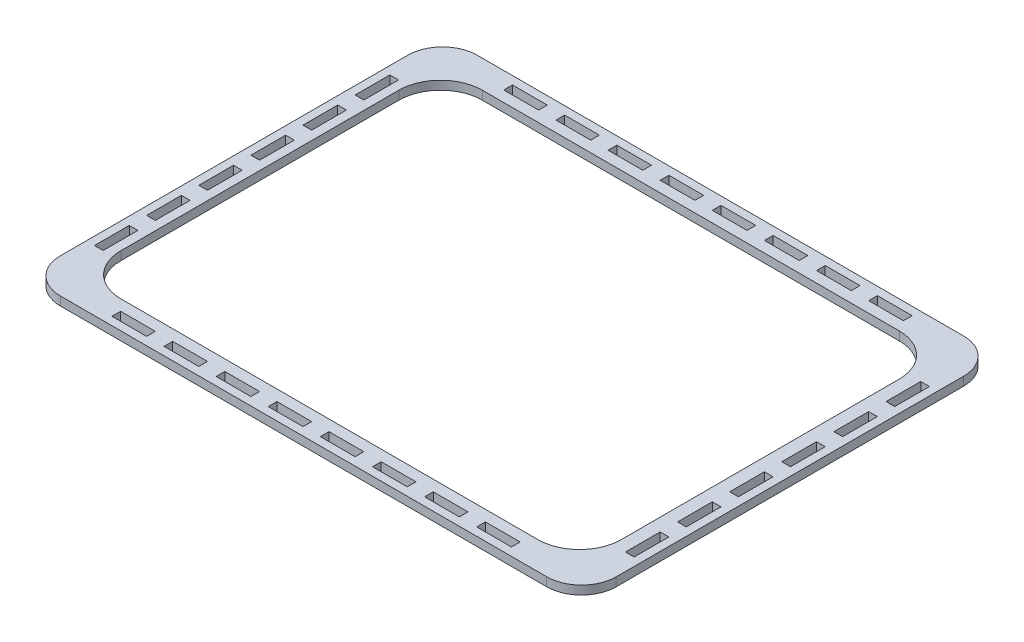
SolidWorks part; units mm, degrees
ref_plane "Front Plane" through (0, 0, 0) normal (0, 0, 1) x (1, 0, 0)
ref_plane "Top Plane" through (0, 0, 0) normal (0, 1, 0) x (1, 0, 0)
ref_plane "Right Plane" through (0, 0, 0) normal (1, 0, 0) x (0, 0, -1)
ref_plane "MaskPlane" through (0, 7.1437, 0) normal (0, 1, 0) x (1, 0, 0)
sketch "Sketch1" plane through (0, 7.1437, 0) normal (0, 1, 0) x (-1, 0, 0)
  line L19 (-90.75, 50.8) -> (-90.75, 0)
  line L25 (-90.75, 50.8) -> (-90.75, 0)
  line L27 (-90.75, 0) -> (-90.75, -50.8)
  line L44 (-101.6, 63.5) -> (-101.6, -63.5) construction
  line L45 (-88.9, -76.2) -> (88.9, -76.2) construction
  line L46 (101.6, -63.5) -> (101.6, 63.5) construction
  line L47 (88.9, 76.2) -> (-88.9, 76.2) construction
  line L52 (-101.6, 63.5) -> (-101.6, -63.5)
  line L53 (-88.9, -76.2) -> (88.9, -76.2)
  line L54 (101.6, -63.5) -> (101.6, 63.5)
  line L55 (88.9, 76.2) -> (-88.9, 76.2)
  line L168 (-90.75, 0) -> (-90.75, -50.8)
  line L176 (-75.5, -66.05) -> (76.9, -66.05)
  line L177 (-75.5, -66.05) -> (76.9, -66.05)
  line L178 (92.15, -50.8) -> (92.15, 50.8)
  line L179 (92.15, -50.8) -> (92.15, 50.8)
  line L180 (76.9, 66.05) -> (-75.5, 66.05)
  line L181 (76.9, 66.05) -> (-75.5, 66.05)
  arc A4 (-88.9, 76.2) -> (-101.6, 63.5) centre (-88.9, 63.5) ccw construction
  arc A6 (-101.6, -63.5) -> (-88.9, -76.2) centre (-88.9, -63.5) ccw construction
  arc A8 (88.9, -76.2) -> (101.6, -63.5) centre (88.9, -63.5) ccw construction
  arc A10 (101.6, 63.5) -> (88.9, 76.2) centre (88.9, 63.5) ccw construction
  arc A16 (-88.9, 76.2) -> (-101.6, 63.5) centre (-88.9, 63.5) ccw
  arc A17 (-101.6, -63.5) -> (-88.9, -76.2) centre (-88.9, -63.5) ccw
  arc A18 (88.9, -76.2) -> (101.6, -63.5) centre (88.9, -63.5) ccw
  arc A19 (101.6, 63.5) -> (88.9, 76.2) centre (88.9, 63.5) ccw
  arc A24 (-90.75, -50.8) -> (-75.5, -66.05) centre (-75.5, -50.8) ccw
  arc A26 (-90.75, -50.8) -> (-75.5, -66.05) centre (-75.5, -50.8) ccw
  arc A132 (76.9, -66.05) -> (92.15, -50.8) centre (76.9, -50.8) ccw
  arc A134 (76.9, -66.05) -> (92.15, -50.8) centre (76.9, -50.8) ccw
  arc A140 (92.15, 50.8) -> (76.9, 66.05) centre (76.9, 50.8) ccw
  arc A141 (92.15, 50.8) -> (76.9, 66.05) centre (76.9, 50.8) ccw
  arc A142 (-75.5, 66.05) -> (-90.75, 50.8) centre (-75.5, 50.8) ccw
  arc A143 (-75.5, 66.05) -> (-90.75, 50.8) centre (-75.5, 50.8) ccw
  dimension "D1" = 3
extrude "FrontFace" add sketch "Sketch1" along normal blind 3.175
sketch "Sketch2" plane through (0, 10.3187, 0) normal (0, 1, 0) x (1, 0, 0)
  line L1 (-98.6155, 53.975) -> (-95.4405, 53.975)
  line L2 (-98.6155, 53.975) -> (-98.6155, -53.975)
  line L3 (-98.6155, -53.975) -> (-95.4405, -53.975)
  line L4 (-95.4405, 53.975) -> (-95.4405, -53.975)
  line L5 (-73.025, -70.0405) -> (73.025, -70.0405)
  line L6 (-73.025, -70.0405) -> (-73.025, -73.2155)
  line L7 (-73.025, -73.2155) -> (73.025, -73.2155)
  line L8 (73.025, -70.0405) -> (73.025, -73.2155)
  line L9 (95.4405, -53.975) -> (98.6155, -53.975)
  line L10 (95.4405, -53.975) -> (95.4405, 53.975)
  line L11 (95.4405, 53.975) -> (98.6155, 53.975)
  line L12 (98.6155, -53.975) -> (98.6155, 53.975)
  line L13 (73.025, 73.2155) -> (-73.025, 73.2155)
  line L14 (73.025, 73.2155) -> (73.025, 70.0405)
  line L15 (73.025, 70.0405) -> (-73.025, 70.0405)
  line L16 (-73.025, 73.2155) -> (-73.025, 70.0405)
  line L132 (95.25, -53.975) -> (101.6, -53.975)
  line L133 (95.25, -60.325) -> (95.25, -53.975)
  line L134 (101.6, -60.325) -> (95.25, -60.325)
  line L135 (101.6, -63.5) -> (101.6, -60.325)
  line L136 (79.375, -76.2) -> (88.9, -76.2)
  line L137 (79.375, -69.85) -> (79.375, -76.2)
  line L138 (73.025, -69.85) -> (79.375, -69.85)
  line L139 (73.025, -76.2) -> (73.025, -69.85)
  line L140 (60.325, -76.2) -> (73.025, -76.2)
  line L141 (60.325, -69.85) -> (60.325, -76.2)
  line L142 (53.975, -69.85) -> (60.325, -69.85)
  line L143 (53.975, -76.2) -> (53.975, -69.85)
  line L144 (41.275, -76.2) -> (53.975, -76.2)
  line L145 (41.275, -69.85) -> (41.275, -76.2)
  line L146 (34.925, -69.85) -> (41.275, -69.85)
  line L147 (34.925, -76.2) -> (34.925, -69.85)
  line L148 (22.225, -76.2) -> (34.925, -76.2)
  line L149 (22.225, -69.85) -> (22.225, -76.2)
  line L150 (15.875, -69.85) -> (22.225, -69.85)
  line L151 (15.875, -76.2) -> (15.875, -69.85)
  line L152 (3.175, -76.2) -> (15.875, -76.2)
  line L153 (3.175, -69.85) -> (3.175, -76.2)
  line L154 (-3.175, -69.85) -> (3.175, -69.85)
  line L155 (-3.175, -76.2) -> (-3.175, -69.85)
  line L156 (-15.875, -76.2) -> (-3.175, -76.2)
  line L157 (-15.875, -69.85) -> (-15.875, -76.2)
  line L158 (-22.225, -69.85) -> (-15.875, -69.85)
  line L159 (-22.225, -76.2) -> (-22.225, -69.85)
  line L160 (-34.925, -76.2) -> (-22.225, -76.2)
  line L161 (-34.925, -69.85) -> (-34.925, -76.2)
  line L162 (-41.275, -69.85) -> (-34.925, -69.85)
  line L163 (-41.275, -76.2) -> (-41.275, -69.85)
  line L164 (-53.975, -76.2) -> (-41.275, -76.2)
  line L165 (-53.975, -69.85) -> (-53.975, -76.2)
  line L166 (-60.325, -69.85) -> (-53.975, -69.85)
  line L167 (-60.325, -76.2) -> (-60.325, -69.85)
  line L168 (-73.025, -76.2) -> (-60.325, -76.2)
  line L169 (-73.025, -69.85) -> (-73.025, -76.2)
  line L170 (-79.375, -69.85) -> (-73.025, -69.85)
  line L171 (-79.375, -76.2) -> (-79.375, -69.85)
  line L172 (-88.9, -76.2) -> (-79.375, -76.2)
  line L173 (-101.6, -60.325) -> (-101.6, -63.5)
  line L174 (-95.25, -60.325) -> (-101.6, -60.325)
  line L175 (-95.25, -53.975) -> (-95.25, -60.325)
  line L176 (-101.6, -53.975) -> (-95.25, -53.975)
  line L177 (-101.6, -41.275) -> (-101.6, -53.975)
  line L178 (-95.25, -41.275) -> (-101.6, -41.275)
  line L179 (-95.25, -34.925) -> (-95.25, -41.275)
  line L180 (-101.6, -34.925) -> (-95.25, -34.925)
  line L181 (-101.6, -22.225) -> (-101.6, -34.925)
  line L182 (-95.25, -22.225) -> (-101.6, -22.225)
  line L183 (-95.25, -15.875) -> (-95.25, -22.225)
  line L184 (-101.6, -15.875) -> (-95.25, -15.875)
  line L185 (-101.6, -3.175) -> (-101.6, -15.875)
  line L186 (-95.25, -3.175) -> (-101.6, -3.175)
  line L187 (-95.25, 3.175) -> (-95.25, -3.175)
  line L188 (-101.6, 3.175) -> (-95.25, 3.175)
  line L189 (-101.6, 15.875) -> (-101.6, 3.175)
  line L190 (-95.25, 15.875) -> (-101.6, 15.875)
  line L191 (-95.25, 22.225) -> (-95.25, 15.875)
  line L192 (-101.6, 22.225) -> (-95.25, 22.225)
  line L193 (-101.6, 34.925) -> (-101.6, 22.225)
  line L194 (-95.25, 34.925) -> (-101.6, 34.925)
  line L195 (-95.25, 41.275) -> (-95.25, 34.925)
  line L196 (-101.6, 41.275) -> (-95.25, 41.275)
  line L197 (-101.6, 53.975) -> (-101.6, 41.275)
  line L198 (-95.25, 53.975) -> (-101.6, 53.975)
  line L199 (-95.25, 60.325) -> (-95.25, 53.975)
  line L200 (-101.6, 60.325) -> (-95.25, 60.325)
  line L201 (-101.6, 63.5) -> (-101.6, 60.325)
  line L202 (-79.375, 76.2) -> (-88.9, 76.2)
  line L203 (-79.375, 69.85) -> (-79.375, 76.2)
  line L204 (-73.025, 69.85) -> (-79.375, 69.85)
  line L205 (-73.025, 76.2) -> (-73.025, 69.85)
  line L206 (-60.325, 76.2) -> (-73.025, 76.2)
  line L207 (-60.325, 69.85) -> (-60.325, 76.2)
  line L208 (-53.975, 69.85) -> (-60.325, 69.85)
  line L209 (-53.975, 76.2) -> (-53.975, 69.85)
  line L210 (-41.275, 76.2) -> (-53.975, 76.2)
  line L211 (-41.275, 69.85) -> (-41.275, 76.2)
  line L212 (-34.925, 69.85) -> (-41.275, 69.85)
  line L213 (-34.925, 76.2) -> (-34.925, 69.85)
  line L214 (-22.225, 76.2) -> (-34.925, 76.2)
  line L215 (-22.225, 69.85) -> (-22.225, 76.2)
  line L216 (-15.875, 69.85) -> (-22.225, 69.85)
  line L217 (-15.875, 76.2) -> (-15.875, 69.85)
  line L218 (-3.175, 76.2) -> (-15.875, 76.2)
  line L219 (-3.175, 69.85) -> (-3.175, 76.2)
  line L220 (3.175, 69.85) -> (-3.175, 69.85)
  line L221 (3.175, 76.2) -> (3.175, 69.85)
  line L222 (15.875, 76.2) -> (3.175, 76.2)
  line L223 (15.875, 69.85) -> (15.875, 76.2)
  line L224 (22.225, 69.85) -> (15.875, 69.85)
  line L225 (22.225, 76.2) -> (22.225, 69.85)
  line L226 (34.925, 76.2) -> (22.225, 76.2)
  line L227 (34.925, 69.85) -> (34.925, 76.2)
  line L228 (41.275, 69.85) -> (34.925, 69.85)
  line L229 (41.275, 76.2) -> (41.275, 69.85)
  line L230 (53.975, 76.2) -> (41.275, 76.2)
  line L231 (53.975, 69.85) -> (53.975, 76.2)
  line L232 (60.325, 69.85) -> (53.975, 69.85)
  line L233 (60.325, 76.2) -> (60.325, 69.85)
  line L234 (73.025, 76.2) -> (60.325, 76.2)
  line L235 (73.025, 69.85) -> (73.025, 76.2)
  line L236 (79.375, 69.85) -> (73.025, 69.85)
  line L237 (79.375, 76.2) -> (79.375, 69.85)
  line L238 (88.9, 76.2) -> (79.375, 76.2)
  line L239 (101.6, 60.325) -> (101.6, 63.5)
  line L240 (95.25, 60.325) -> (101.6, 60.325)
  line L241 (95.25, 53.975) -> (95.25, 60.325)
  line L242 (101.6, 53.975) -> (95.25, 53.975)
  line L243 (101.6, 41.275) -> (101.6, 53.975)
  line L244 (95.25, 41.275) -> (101.6, 41.275)
  line L245 (95.25, 34.925) -> (95.25, 41.275)
  line L246 (101.6, 34.925) -> (95.25, 34.925)
  line L247 (101.6, 22.225) -> (101.6, 34.925)
  line L248 (95.25, 22.225) -> (101.6, 22.225)
  line L249 (95.25, 15.875) -> (95.25, 22.225)
  line L250 (101.6, 15.875) -> (95.25, 15.875)
  line L251 (101.6, 3.175) -> (101.6, 15.875)
  line L252 (95.25, 3.175) -> (101.6, 3.175)
  line L253 (95.25, -3.175) -> (95.25, 3.175)
  line L254 (101.6, -3.175) -> (95.25, -3.175)
  line L255 (101.6, -15.875) -> (101.6, -3.175)
  line L256 (95.25, -15.875) -> (101.6, -15.875)
  line L257 (95.25, -22.225) -> (95.25, -15.875)
  line L258 (101.6, -22.225) -> (95.25, -22.225)
  line L259 (101.6, -34.925) -> (101.6, -22.225)
  line L260 (95.25, -34.925) -> (101.6, -34.925)
  line L261 (95.25, -41.275) -> (95.25, -34.925)
  line L262 (101.6, -41.275) -> (95.25, -41.275)
  line L263 (101.6, -53.975) -> (101.6, -41.275)
  line L264 (95.25, -53.975) -> (101.6, -53.975)
  line L265 (95.25, -60.325) -> (95.25, -53.975)
  line L266 (101.6, -60.325) -> (95.25, -60.325)
  line L267 (101.6, -63.5) -> (101.6, -60.325)
  line L268 (79.375, -76.2) -> (88.9, -76.2)
  line L269 (79.375, -69.85) -> (79.375, -76.2)
  line L270 (73.025, -69.85) -> (79.375, -69.85)
  line L271 (73.025, -76.2) -> (73.025, -69.85)
  line L272 (60.325, -76.2) -> (73.025, -76.2)
  line L273 (60.325, -69.85) -> (60.325, -76.2)
  line L274 (53.975, -69.85) -> (60.325, -69.85)
  line L275 (53.975, -76.2) -> (53.975, -69.85)
  line L276 (41.275, -76.2) -> (53.975, -76.2)
  line L277 (41.275, -69.85) -> (41.275, -76.2)
  line L278 (34.925, -69.85) -> (41.275, -69.85)
  line L279 (34.925, -76.2) -> (34.925, -69.85)
  line L280 (22.225, -76.2) -> (34.925, -76.2)
  line L281 (22.225, -69.85) -> (22.225, -76.2)
  line L282 (15.875, -69.85) -> (22.225, -69.85)
  line L283 (15.875, -76.2) -> (15.875, -69.85)
  line L284 (3.175, -76.2) -> (15.875, -76.2)
  line L285 (3.175, -69.85) -> (3.175, -76.2)
  line L286 (-3.175, -69.85) -> (3.175, -69.85)
  line L287 (-3.175, -76.2) -> (-3.175, -69.85)
  line L288 (-15.875, -76.2) -> (-3.175, -76.2)
  line L289 (-15.875, -69.85) -> (-15.875, -76.2)
  line L290 (-22.225, -69.85) -> (-15.875, -69.85)
  line L291 (-22.225, -76.2) -> (-22.225, -69.85)
  line L292 (-34.925, -76.2) -> (-22.225, -76.2)
  line L293 (-34.925, -69.85) -> (-34.925, -76.2)
  line L294 (-41.275, -69.85) -> (-34.925, -69.85)
  line L295 (-41.275, -76.2) -> (-41.275, -69.85)
  line L296 (-53.975, -76.2) -> (-41.275, -76.2)
  line L297 (-53.975, -69.85) -> (-53.975, -76.2)
  line L298 (-60.325, -69.85) -> (-53.975, -69.85)
  line L299 (-60.325, -76.2) -> (-60.325, -69.85)
  line L300 (-73.025, -76.2) -> (-60.325, -76.2)
  line L301 (-73.025, -69.85) -> (-73.025, -76.2)
  line L302 (-79.375, -69.85) -> (-73.025, -69.85)
  line L303 (-79.375, -76.2) -> (-79.375, -69.85)
  line L304 (-88.9, -76.2) -> (-79.375, -76.2)
  line L305 (-101.6, -60.325) -> (-101.6, -63.5)
  line L306 (-95.25, -60.325) -> (-101.6, -60.325)
  line L307 (-95.25, -53.975) -> (-95.25, -60.325)
  line L308 (-101.6, -53.975) -> (-95.25, -53.975)
  line L309 (-101.6, -41.275) -> (-101.6, -53.975)
  line L310 (-95.25, -41.275) -> (-101.6, -41.275)
  line L311 (-95.25, -34.925) -> (-95.25, -41.275)
  line L312 (-101.6, -34.925) -> (-95.25, -34.925)
  line L313 (-101.6, -22.225) -> (-101.6, -34.925)
  line L314 (-95.25, -22.225) -> (-101.6, -22.225)
  line L315 (-95.25, -15.875) -> (-95.25, -22.225)
  line L316 (-101.6, -15.875) -> (-95.25, -15.875)
  line L317 (-101.6, -3.175) -> (-101.6, -15.875)
  line L318 (-95.25, -3.175) -> (-101.6, -3.175)
  line L319 (-95.25, 3.175) -> (-95.25, -3.175)
  line L320 (-101.6, 3.175) -> (-95.25, 3.175)
  line L321 (-101.6, 15.875) -> (-101.6, 3.175)
  line L322 (-95.25, 15.875) -> (-101.6, 15.875)
  line L323 (-95.25, 22.225) -> (-95.25, 15.875)
  line L324 (-101.6, 22.225) -> (-95.25, 22.225)
  line L325 (-101.6, 34.925) -> (-101.6, 22.225)
  line L326 (-95.25, 34.925) -> (-101.6, 34.925)
  line L327 (-95.25, 41.275) -> (-95.25, 34.925)
  line L328 (-101.6, 41.275) -> (-95.25, 41.275)
  line L329 (-101.6, 53.975) -> (-101.6, 41.275)
  line L330 (-95.25, 53.975) -> (-101.6, 53.975)
  line L331 (-95.25, 60.325) -> (-95.25, 53.975)
  line L332 (-101.6, 60.325) -> (-95.25, 60.325)
  line L333 (-101.6, 63.5) -> (-101.6, 60.325)
  line L334 (-79.375, 76.2) -> (-88.9, 76.2)
  line L335 (-79.375, 69.85) -> (-79.375, 76.2)
  line L336 (-73.025, 69.85) -> (-79.375, 69.85)
  line L337 (-73.025, 76.2) -> (-73.025, 69.85)
  line L338 (-60.325, 76.2) -> (-73.025, 76.2)
  line L339 (-60.325, 69.85) -> (-60.325, 76.2)
  line L340 (-53.975, 69.85) -> (-60.325, 69.85)
  line L341 (-53.975, 76.2) -> (-53.975, 69.85)
  line L342 (-41.275, 76.2) -> (-53.975, 76.2)
  line L343 (-41.275, 69.85) -> (-41.275, 76.2)
  line L344 (-34.925, 69.85) -> (-41.275, 69.85)
  line L345 (-34.925, 76.2) -> (-34.925, 69.85)
  line L346 (-22.225, 76.2) -> (-34.925, 76.2)
  line L347 (-22.225, 69.85) -> (-22.225, 76.2)
  line L348 (-15.875, 69.85) -> (-22.225, 69.85)
  line L349 (-15.875, 76.2) -> (-15.875, 69.85)
  line L350 (-3.175, 76.2) -> (-15.875, 76.2)
  line L351 (-3.175, 69.85) -> (-3.175, 76.2)
  line L352 (3.175, 69.85) -> (-3.175, 69.85)
  line L353 (3.175, 76.2) -> (3.175, 69.85)
  line L354 (15.875, 76.2) -> (3.175, 76.2)
  line L355 (15.875, 69.85) -> (15.875, 76.2)
  line L356 (22.225, 69.85) -> (15.875, 69.85)
  line L357 (22.225, 76.2) -> (22.225, 69.85)
  line L358 (34.925, 76.2) -> (22.225, 76.2)
  line L359 (34.925, 69.85) -> (34.925, 76.2)
  line L360 (41.275, 69.85) -> (34.925, 69.85)
  line L361 (41.275, 76.2) -> (41.275, 69.85)
  line L362 (53.975, 76.2) -> (41.275, 76.2)
  line L363 (53.975, 69.85) -> (53.975, 76.2)
  line L364 (60.325, 69.85) -> (53.975, 69.85)
  line L365 (60.325, 76.2) -> (60.325, 69.85)
  line L366 (73.025, 76.2) -> (60.325, 76.2)
  line L367 (73.025, 69.85) -> (73.025, 76.2)
  line L368 (79.375, 69.85) -> (73.025, 69.85)
  line L369 (79.375, 76.2) -> (79.375, 69.85)
  line L370 (88.9, 76.2) -> (79.375, 76.2)
  line L371 (101.6, 60.325) -> (101.6, 63.5)
  line L372 (95.25, 60.325) -> (101.6, 60.325)
  line L373 (95.25, 53.975) -> (95.25, 60.325)
  line L374 (101.6, 53.975) -> (95.25, 53.975)
  line L375 (101.6, 41.275) -> (101.6, 53.975)
  line L376 (95.25, 41.275) -> (101.6, 41.275)
  line L377 (95.25, 34.925) -> (95.25, 41.275)
  line L378 (101.6, 34.925) -> (95.25, 34.925)
  line L379 (101.6, 22.225) -> (101.6, 34.925)
  line L380 (95.25, 22.225) -> (101.6, 22.225)
  line L381 (95.25, 15.875) -> (95.25, 22.225)
  line L382 (101.6, 15.875) -> (95.25, 15.875)
  line L383 (101.6, 3.175) -> (101.6, 15.875)
  line L384 (95.25, 3.175) -> (101.6, 3.175)
  line L385 (95.25, -3.175) -> (95.25, 3.175)
  line L386 (101.6, -3.175) -> (95.25, -3.175)
  line L387 (101.6, -15.875) -> (101.6, -3.175)
  line L388 (95.25, -15.875) -> (101.6, -15.875)
  line L389 (95.25, -22.225) -> (95.25, -15.875)
  line L390 (101.6, -22.225) -> (95.25, -22.225)
  line L391 (101.6, -34.925) -> (101.6, -22.225)
  line L392 (95.25, -34.925) -> (101.6, -34.925)
  line L393 (95.25, -41.275) -> (95.25, -34.925)
  line L394 (101.6, -41.275) -> (95.25, -41.275)
  line L395 (101.6, -53.975) -> (101.6, -41.275)
  arc A4 (88.9, -76.2) -> (101.6, -63.5) centre (88.9, -63.5) ccw
  arc A5 (-101.6, -63.5) -> (-88.9, -76.2) centre (-88.9, -63.5) ccw
  arc A6 (-88.9, 76.2) -> (-101.6, 63.5) centre (-88.9, 63.5) ccw
  arc A7 (101.6, 63.5) -> (88.9, 76.2) centre (88.9, 63.5) ccw
  arc A8 (88.9, -76.2) -> (101.6, -63.5) centre (88.9, -63.5) ccw
  arc A9 (-101.6, -63.5) -> (-88.9, -76.2) centre (-88.9, -63.5) ccw
  arc A10 (-88.9, 76.2) -> (-101.6, 63.5) centre (-88.9, 63.5) ccw
  arc A11 (101.6, 63.5) -> (88.9, 76.2) centre (88.9, 63.5) ccw
  dimension "D2" = 3.175
  dimension "D3" = 2.9845
  dimension "D4" = 3.175
  dimension "D5" = 2.9845
  dimension "D6" = 2.9845
  dimension "D7" = 3.175
  dimension "D8" = 2.9845
  dimension "D9" = 3.175
  dimension "D1" = 0
extrude "Cut-Extrude2" cut sketch "Sketch2" against normal up to surface (3.175 mm away) contours L2 L328 L4 L1 | L4 L326 L2 L324 | L4 L322 L2 L320 | L4 L318 L2 L316 | L4 L314 L2 L312 | L4 L310 L2 L3 | L7 L299 L5 L6 | L5 L297 L7 L295 | L5 L293 L7 L291 | L5 L289 L7 L287 | L5 L285 L7 L283 | L5 L281 L7 L279 | L5 L277 L7 L275 | L5 L273 L7 L8 | L12 L394 L10 L9 | L10 L392 L12 L390 | L10 L388 L12 L386 | L10 L384 L12 L382 | L10 L380 L12 L378 | L10 L376 L12 L11 | L13 L365 L15 L14 | L15 L363 L13 L361 | L15 L359 L13 L357 | L15 L355 L13 L353 | L15 L351 L13 L349 | L15 L347 L13 L345 | L15 L343 L13 L341 | L15 L339 L13 L16 region at (-97.028, 10.3187, -47.625) region at (-97.028, 10.3187, -28.575) region at (-97.028, 10.3187, -9.525) region at (-97.028, 10.3187, 9.525) region at (-97.028, 10.3187, 28.575) region at (-66.675, 10.3187, -71.628) region at (-97.028, 10.3187, 47.625) region at (-47.625, 10.3187, -71.628) region at (-28.575, 10.3187, -71.628) region at (-9.525, 10.3187, -71.628) region at (9.525, 10.3187, -71.628) region at (28.575, 10.3187, -71.628) region at (-66.675, 10.3187, 71.628) region at (47.625, 10.3187, -71.628) region at (-47.625, 10.3187, 71.628) region at (66.675, 10.3187, -71.628) region at (-28.575, 10.3187, 71.628) region at (-9.525, 10.3187, 71.628) region at (9.525, 10.3187, 71.628) region at (28.575, 10.3187, 71.628) region at (47.625, 10.3187, 71.628) region at (97.028, 10.3187, -47.625) region at (66.675, 10.3187, 71.628) region at (97.028, 10.3187, -28.575) region at (97.028, 10.3187, -9.525) region at (97.028, 10.3187, 9.525) region at (97.028, 10.3187, 28.575) region at (97.028, 10.3187, 47.625) up to face at (0, 7.1437, 0)
equation "\"ShellWallThickness\"=0.115"
equation "\"ShellOverlap\"=0.625"
